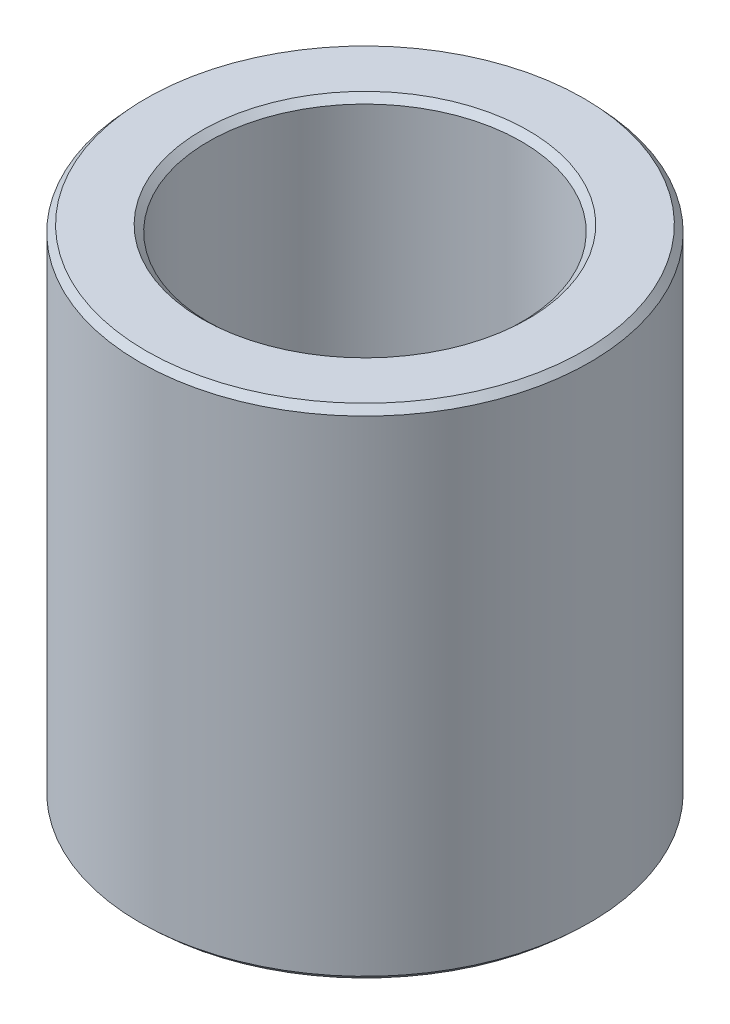
SolidWorks part; units mm, degrees
ref_plane "Front Plane" through (0, 0, 0) normal (0, 0, 1) x (1, 0, 0)
ref_plane "Top Plane" through (0, 0, 0) normal (0, 1, 0) x (1, 0, 0)
ref_plane "Right Plane" through (0, 0, 0) normal (1, 0, 0) x (0, 0, -1)
sketch "Sketch1" plane through (0, 0, 0) normal (0, 1, 0) x (1, 0, 0)
  circle A0 centre (0, 0) radius 22.5
  dimension "SLEEVE_OD" = 45
extrude "Boss-Extrude1" add sketch "Sketch1" along normal blind 49.8069
sketch "Sketch2" plane through (0, 0, 0) normal (0, 1, 0) x (1, 0, 0)
  circle A0 centre (0, 0) radius 15.6463
  dimension "BORE_D" = 31.2925
extrude "Cut-Extrude1" cut sketch "Sketch2" along normal through all
chamfer "Chamfer1" distance 0.6745 angle 42.718 4 edges at (0, 49.8069, 15.6463) (0, 0, 15.6463) (0, 0, 22.5) (0, 49.8069, 22.5) first distance on face at (0, 49.8069, 15.6463) first distance on face at (0, 0, 15.6463) first distance on face at (0, 49.8069, 22.5)
